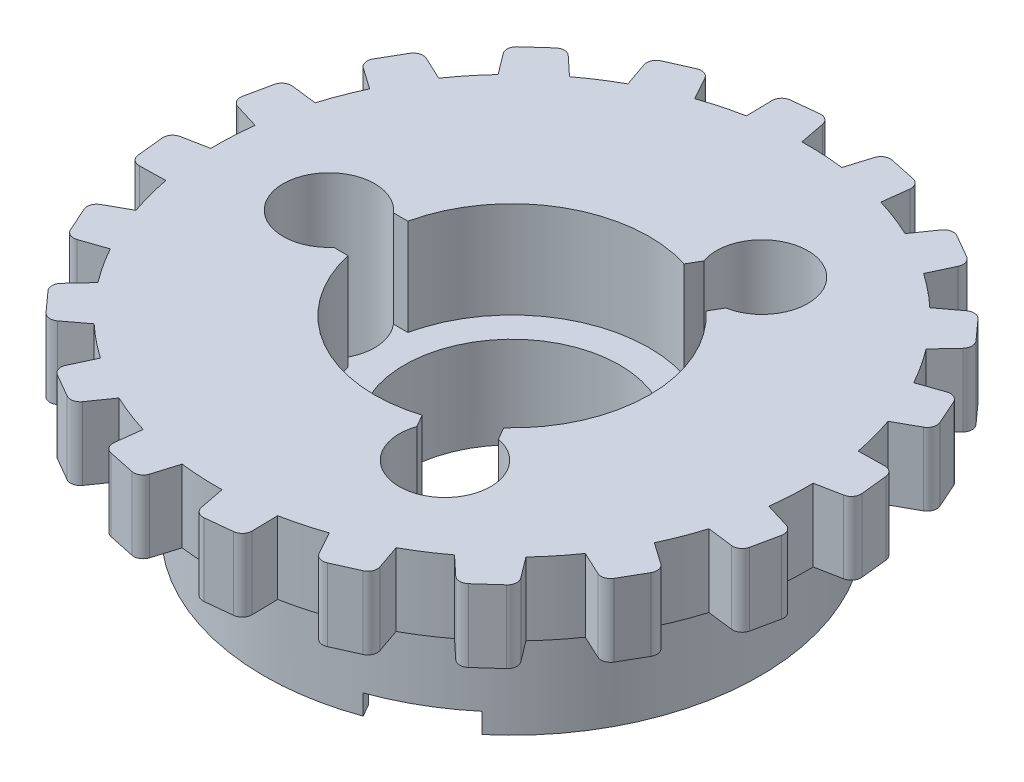
SolidWorks part; units mm, degrees
ref_plane "Front Plane" through (0, 0, 0) normal (0, 0, 1) x (1, 0, 0)
ref_plane "Top Plane" through (0, 0, 0) normal (0, 1, 0) x (1, 0, 0)
ref_plane "Right Plane" through (0, 0, 0) normal (1, 0, 0) x (0, 0, -1)
sketch "Sketch2" plane through (0, 0, 0) normal (0, 1, 0) x (1, 0, 0)
  circle A0 centre (0, 0) radius 30.764
  circle A1 centre (-19.0525, 0) radius 4.7625
  circle A2 centre (9.5262, 16.4999) radius 4.7625
  circle A3 centre (9.5262, -16.4999) radius 4.7625
  circle A5 centre (0, 0) radius 11.2
  point P2 (0, 0)
  point P11 (0, 0)
  point P12 (13.6656, 4.178)
  dimension "D2" = 3
  dimension "D1" = 22.4
  dimension "D4" = 61.528
  dimension "D5" = 9.525
extrude "Boss-Extrude2" add sketch "Sketch2" along normal blind 7.55
sketch "Sketch4" plane through (0, 0, 0) normal (0, -1, 0) x (1, 0, 0)
  circle A0 centre (9.5262, 16.4999) radius 4.7625 construction
  circle A1 centre (9.5262, 16.4999) radius 4.7625
  circle A2 centre (0, 0) radius 11.2
  circle A19 centre (0, 0) radius 25.815
  point P6 (-1.3086, -0.0126)
  point P13 (12.187, -21.1085)
  point P15 (-24.374, 0)
  point P17 (12.187, 21.1085)
  point P18 (-12.5475, 0)
  point P25 (16.9495, -21.1085)
  point P26 (16.9495, 21.1085)
  point P27 (-26.7552, 4.1244)
  point P28 (9.8057, 25.2329)
  point P29 (9.8057, -25.2329)
  point P30 (-26.7552, -4.1244)
  point P31 (16.4175, -16.723)
  point P36 (16.4175, 16.723)
  point P46 (13.9118, 4.2533)
  circle M1 centre (9.5262, -16.4999) radius 4.7625
  circle M2 centre (-19.0525, 0) radius 4.7625
  circle M4 centre (0, 0) radius 11.2
  circle M5 centre (9.5262, 16.4999) radius 4.7625
  dimension "D1" = 22.4
extrude "Boss-Extrude3" add sketch "Sketch4" along normal blind 12 contours A19 M1 M5 M4 M2 region at (-25.0848, 0, 0)
sketch "Sketch7" plane through (0, 7.55, 0) normal (0, 1, 0) x (1, 0, 0)
  line L0 (0, 0) -> (9.5262, 16.4999) construction
  line L1 (9.6653, -10.5221) -> (10.4153, -11.8212)
  line L2 (9.6653, 10.5221) -> (10.4153, 11.8212)
  line L4 (4.2798, -13.6314) -> (5.0298, -14.9305)
  line L5 (-13.9451, -3.1093) -> (-15.4451, -3.1093)
  line L6 (-13.9451, 3.1093) -> (-15.4451, 3.1093)
  line L7 (4.2798, 13.6314) -> (5.0298, 14.9305)
  arc A0 (4.2798, 13.6314) -> (-13.9451, 3.1093) centre (0, 0) ccw
  arc A1 (10.4153, -11.8212) -> (5.0298, -14.9305) centre (9.5262, -16.4999) ccw
  arc A2 (-15.4451, -3.1093) -> (-15.4451, 3.1093) centre (-19.0525, 0) ccw
  circle A4 centre (9.5262, 16.4999) radius 4.7625 construction
  arc A5 (5.0298, 14.9305) -> (10.4153, 11.8212) centre (9.5262, 16.4999) ccw
  arc A6 (-13.9451, -3.1093) -> (4.2798, -13.6314) centre (0, 0) ccw
  arc A8 (9.6653, -10.5221) -> (9.6653, 10.5221) centre (0, 0) ccw
  point P21 (0, 0)
  point P28 (0, 0)
  point P29 (0, 0)
  dimension "D1" = 28.575
  dimension "D2" = 3
extrude "Cut-Extrude7" cut sketch "Sketch7" against normal blind 10.028
sketch "Sketch8" plane through (0, 7.55, 0) normal (0, 1, 0) x (1, 0, 0)
  line L0 (0, 0) -> (26.6173, 46.1024) construction
  line L2 (2.3314, 34.1772) -> (21.2283, 23.2671) construction
  line L3 (13.0466, 27.8605) -> (14.6011, 30.0806)
  line L4 (15.9203, 30.3731) -> (18.3437, 28.9739)
  line L5 (17.6046, 25.229) -> (18.75, 27.6853)
  circle A0 centre (0, 0) radius 30.764 construction
  arc A1 (14.6011, 30.0806) -> (15.9203, 30.3731) centre (15.4203, 29.5071) cw
  arc A3 (18.75, 27.6853) -> (18.3437, 28.9739) centre (17.8437, 28.1079) ccw
  point P18 (17.132, 29.6735)
  point P124 (0, 0)
  circle M13 centre (0, 0) radius 30.764
  dimension "D4" = 1
  dimension "D1" = 3.5
  dimension "D2" = 85
  dimension "D5" = 2.6316
extrude "Boss-Extrude4" add sketch "Sketch8" against normal up to surface (7.55 mm away) contours M13 | L5 A3 L4 A1 L3 M13 | M13 | M13 | M13 | M13 | M13 | M13 | M13 | M13 | M13 | M13 | M13 | M13 region at (16.2127, 7.55, -28.0813) up to face at (0, 0, 30.764)
pattern_circular "CirPattern1" count 20 over 360 about axis through (0, 7.55, 0) along (0, -1, 0) of "Boss-Extrude4"
sketch "Sketch9" plane through (0, -12, 0) normal (0, -1, 0) x (1, 0, 0)
  line L0 (9.5262, -16.4999) -> (0, 0) construction
  line L1 (8.0389, -22.9738) -> (8.7889, -24.2728)
  line L2 (15.8764, -18.4488) -> (16.6264, -19.7478)
  line L3 (-23.9153, 4.525) -> (-25.4153, 4.525)
  line L4 (-23.9153, -4.525) -> (-25.4153, -4.525)
  line L5 (15.8764, 18.4488) -> (16.6264, 19.7478)
  line L6 (8.0389, 22.9738) -> (8.7889, 24.2728)
  arc A2 (-23.9153, -4.525) -> (-23.9153, 4.525) centre (-19.0525, 0) ccw
  arc A3 (16.1687, -16.4999) -> (16.1687, -16.4999) centre (9.5262, -16.4999) ccw
  arc A4 (15.8764, -18.4488) -> (8.0389, -22.9738) centre (9.5262, -16.4999) ccw
  arc A5 (-25.4153, 4.525) -> (-25.4153, -4.525) centre (0, 0) ccw
  circle A6 centre (0, 0) radius 25.815 construction
  arc A7 (8.7889, -24.2728) -> (16.6264, -19.7478) centre (0, 0) ccw
  arc A8 (8.0389, 22.9738) -> (15.8764, 18.4488) centre (9.5263, 16.4999) ccw
  arc A9 (16.6264, 19.7478) -> (8.7889, 24.2728) centre (0, 0) ccw
  point P9 (0, 0)
  point P22 (0, 0)
  dimension "D1" = 1.88
  dimension "D2" = 3
extrude "Cut-Extrude8" cut sketch "Sketch9" against normal blind 2.0875
